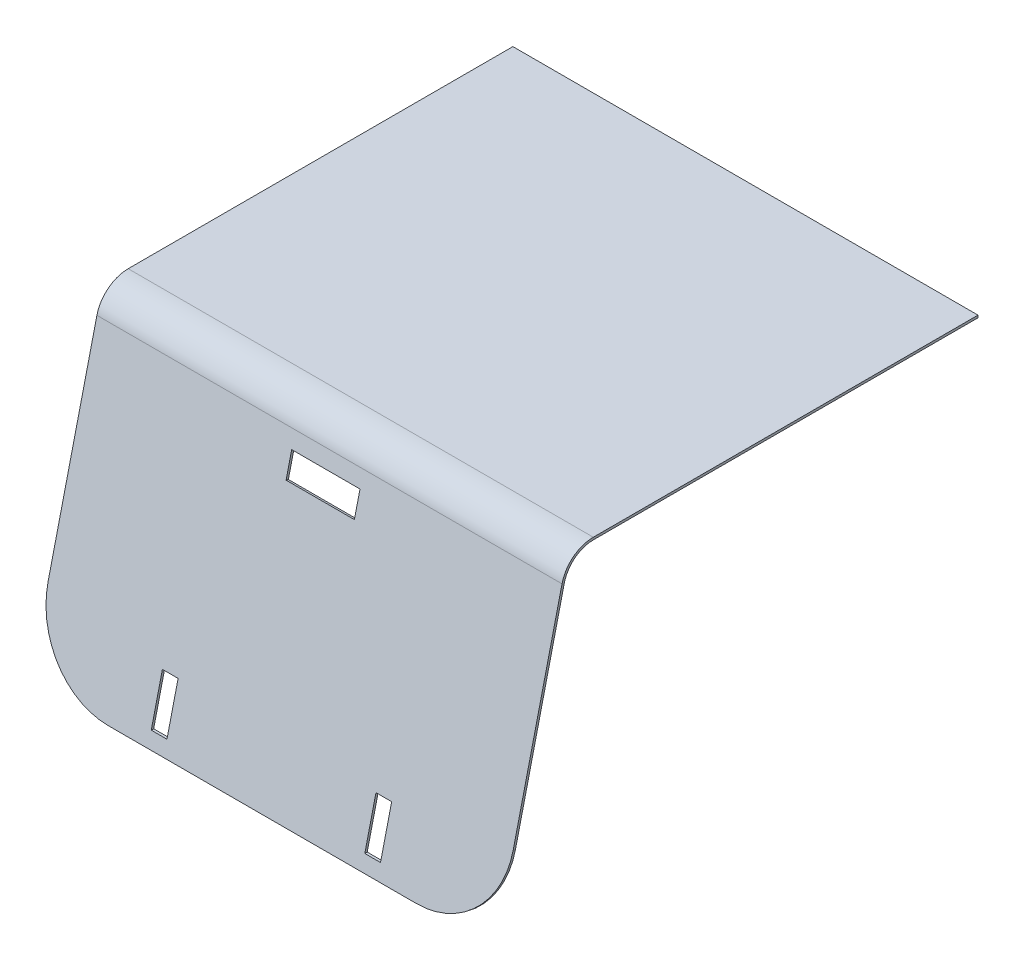
SolidWorks part; units mm, degrees
material "6061 합금"
ref_plane "정면" through (0, 0, 0) normal (0, 0, 1) x (1, 0, 0)
ref_plane "윗면" through (0, 0, 0) normal (0, 1, 0) x (1, 0, 0)
ref_plane "우측면" through (0, 0, 0) normal (1, 0, 0) x (0, 0, -1)
sketch "스케치2" plane through (0, 0, 0) normal (1, 0, 0) x (0, 0, -1)
  line L0 (-245.0866, 321.4745) -> (-245.0866, -319.7255) construction
  line L1 (-215.0866, 321.4745) -> (-215.0866, -319.7255) construction
  line L2 (244.9134, 321.4745) -> (244.9134, -159.7255) construction
  line L3 (214.9134, 321.4745) -> (214.9134, -159.7255) construction
  line L4 (-245.0866, -129.7255) -> (244.9134, -129.7255) construction
  line L5 (-245.0866, -159.7255) -> (244.9134, -159.7255) construction
  line L6 (-245.0866, 20.2745) -> (244.9134, 20.2745) construction
  line L7 (-245.0866, -9.7255) -> (244.9134, -9.7255) construction
  line L8 (-245.0866, 101.2745) -> (244.9134, 101.2745) construction
  line L9 (-245.0866, 71.2745) -> (244.9134, 71.2745) construction
  line L10 (44.9134, -319.7255) -> (44.9134, -129.7255) construction
  line L11 (14.9134, -129.7255) -> (14.9134, -319.7255) construction
  line L12 (154.9134, -129.7255) -> (154.9134, -159.7255) construction
  line L13 (124.9134, -129.7255) -> (124.9134, -159.7255) construction
  line L14 (-180.0866, -285.7255) -> (-180.0866, -319.7255) construction
  line L15 (-180.0866, -319.7255) -> (-120.0866, -319.7255) construction
  line L16 (-120.0866, -319.7255) -> (-120.0866, -285.7255) construction
  line L17 (-248.0866, -129.7255) -> (-317.0866, -129.7255) construction
  line L18 (-317.0866, -129.7255) -> (-317.0866, -124.7255) construction
  line L19 (-317.0866, -124.7255) -> (-245.0866, -124.7255) construction
  line L20 (-248.0866, -79.7255) -> (-248.0866, -129.7255) construction
  line L21 (-317.0866, -124.7255) -> (-317.0866, -79.7255) construction
  line L22 (-317.0866, -79.7255) -> (-248.0866, -79.7255) construction
  line L23 (-366.6673, -141.9832) -> (-319.0575, -312.6598) construction
  line L24 (-309.7511, -319.7255) -> (44.9134, -319.7255) construction
  line L25 (-245.0866, 321.4745) -> (244.9134, 321.4745) construction
  line L26 (-357.3609, -129.7255) -> (-248.0866, -129.7255) construction
  line L27 (-248.0866, -79.7255) -> (-357.8699, -79.7255) construction
  line L28 (-281.0866, -124.7255) -> (-281.0866, -79.7255) construction
  line L29 (-367.2716, -67.8376) -> (-281.9991, 292.2817) construction
  line L30 (-245.0866, 20.2745) -> (-346.4076, 20.2745) construction
  line L31 (281.0076, 291.6281) -> (365.9454, -152.5713) construction
  line L32 (360.9237, -163.222) -> (101.231, -305.3247) construction
  line L33 (-347.8609, 9.7969) -> (-359.3573, -38.7543) construction
  line L34 (-367.2716, -67.8376) -> (-370.1909, -67.1464)
  line L36 (-370.1909, -67.1464) -> (-284.9184, 292.973)
  line L37 (-245.0866, 324.4745) -> (244.9134, 324.4745)
  line L43 (244.9134, 324.4745) -> (244.9134, 321.4745)
  line L45 (244.9134, 321.4745) -> (-245.0866, 321.4745)
  line L48 (-281.9991, 292.2817) -> (-367.2716, -67.8376)
  arc A0 (-120.0866, -285.7255) -> (-180.0866, -285.7255) centre (-150.0866, -285.7255) ccw construction
  arc A1 (-309.7511, -319.7255) -> (-319.0575, -312.6598) centre (-309.7511, -310.0638) cw construction
  arc A2 (-366.6673, -141.9832) -> (-357.3609, -129.7255) centre (-357.3609, -139.3872) cw construction
  arc A3 (-357.8699, -79.7255) -> (-367.2716, -67.8376) centre (-357.8699, -70.0638) cw construction
  arc A4 (365.9454, -152.5713) -> (360.9237, -163.222) centre (356.1234, -154.4495) cw construction
  arc A5 (281.0076, 291.6281) -> (244.9134, 321.4745) centre (244.9134, 284.7263) ccw construction
  arc A6 (44.9134, -319.7255) -> (101.231, -305.3247) centre (44.9134, -202.4043) ccw construction
  arc A7 (-245.0866, 321.4745) -> (-281.9991, 292.2817) centre (-245.0866, 283.5412) ccw construction
  arc A8 (-284.9184, 292.973) -> (-245.0866, 324.4745) centre (-245.0866, 283.5412) cw
  arc A10 (-281.9991, 292.2817) -> (-245.0866, 321.4745) centre (-245.0866, 283.5412) cw
  point P28 (154.9134, -144.7255)
  point P46 (-275.0866, 321.4745)
  point P56 (274.9134, 321.4745)
  point P57 (74.9134, -319.7255)
  dimension "D14" = 60
  dimension "D18" = 30
  dimension "D19" = 30
  dimension "D20" = 30
  dimension "D21" = 10
  dimension "D1" = 30
  dimension "D2" = 490
  dimension "D3" = 30
  dimension "D4" = 30
  dimension "D5" = 150
  dimension "D6" = 30
  dimension "D7" = 81
  dimension "D8" = 30
  dimension "D9" = 290
  dimension "D10" = 30
  dimension "D11" = 110
  dimension "D12" = 30
  dimension "D13" = 95
  dimension "D15" = 72
  dimension "D16" = 5
  dimension "D17" = 45
  dimension "D22" = 3
  dimension "D23" = 72
  dimension "D24" = 1
  dimension "D25" = 3
extrude "보스-돌출1" add sketch "스케치2" along normal blind 296.2 and the other way blind 296.2 contours L48 A10 L45 L43 L37 A8 L36 L34 region at (0, -60.3927, 367.0502)
ref_plane "평면1" through (0, 0, 380) normal (0, 0, 1) x (1, 0, 0)
sketch "스케치3" plane through (0, 0, 380) normal (0, 0, 1) x (1, 0, 0)
  line L0 (-206, 20.9636) -> (206, 20.9636)
  line L1 (0, 20.9636) -> (0, -28.2188) construction
  line L2 (-146, 10.9636) -> (-126, 10.9636)
  line L3 (-146, 10.9636) -> (-146, -49.0364)
  line L4 (-146, -49.0364) -> (-126, -49.0364)
  line L5 (-126, 10.9636) -> (-126, -49.0364)
  line L6 (146, -49.0364) -> (126, -49.0364)
  line L7 (126, 10.9636) -> (126, -49.0364)
  line L8 (146, 10.9636) -> (126, 10.9636)
  line L9 (146, 10.9636) -> (146, -49.0364)
  line L11 (-298, -67.1464) -> (298, -67.1464)
  line L13 (-43.5, 278.473) -> (43.5, 278.473)
  line L14 (-43.5, 278.473) -> (-43.5, 247.473)
  line L15 (-43.5, 247.473) -> (43.5, 247.473)
  line L16 (43.5, 278.473) -> (43.5, 247.473)
  line L17 (-43.5, 278.473) -> (43.5, 247.473) construction
  line L18 (-43.5, 247.473) -> (43.5, 278.473) construction
  line L19 (-296.2, 292.973) -> (296.2, 292.973) construction
  line L21 (-296.2, -67.1464) -> (296.2, -67.1464) construction
  point P12 (0, 262.973)
  dimension "D1" = 60
  dimension "D2" = 20
  dimension "D3" = 10
  dimension "D4" = 126
  dimension "D5" = 88.11
  dimension "D6" = 31
  dimension "D7" = 87
  dimension "D8" = 30
extrude "컷-돌출1" cut sketch "스케치3" against normal up to next contours L9 L8 L7 L6 | L5 L2 L3 L4 region at (-136, -19.0364, 380) region at (136, -19.0364, 380)
ref_plane "평면2" through (0, -70, 0) normal (0, 1, 0) x (1, 0, 0)
fillet "필렛1" radius 100 2 edges at (-296.2, -67.492, 368.7313) (296.2, -67.492, 368.7313)
sketch "스케치10" plane through (0, 79.4385, 335.4811) normal (0, 0.2304, 0.9731) x (1, 0, 0)
  line L0 (0, -0.3516) -> (0, 211.5094) construction
  line L1 (-43.5, 199.4392) -> (43.5, 199.4392)
  line L2 (-43.5, 199.4392) -> (-43.5, 168.4392)
  line L3 (-43.5, 168.4392) -> (43.5, 168.4392)
  line L4 (43.5, 199.4392) -> (43.5, 168.4392)
  line L5 (-43.5, 199.4392) -> (43.5, 168.4392) construction
  line L6 (-43.5, 168.4392) -> (43.5, 199.4392) construction
  line L7 (-296.2, 219.4392) -> (296.2, 219.4392) construction
  point P2 (0, 183.9392)
  dimension "D1" = 31
  dimension "D2" = 87
  dimension "D3" = 20
extrude "컷-돌출2" cut sketch "스케치10" against normal up to next
sketch "스케치11" plane through (0, 79.4385, 335.4811) normal (0, 0.2304, 0.9731) x (1, 0, 0)
  line L5 (251.9, -150.6382) -> (251.9, -12.8916) construction
  line L6 (196.2, -50.6382) -> (266.9107, -121.3489) construction
  line L7 (238.9, -86.8382) -> (238.9, -81.8382) construction
  line L8 (241.9, -104.8382) -> (261.9, -104.8382) construction
  line L9 (241.9, -104.8382) -> (241.9, -107.8382) construction
  line L11 (293.8674, -150.6382) -> (296.2, -150.6382) construction
  line L12 (296.2, -150.6382) -> (296.2, 219.4392) construction
  line L13 (241.9, -107.8382) -> (261.9, -107.8382) construction
  line L14 (261.9, -104.8382) -> (261.9, -107.8382) construction
  line L15 (241.9, -104.8382) -> (261.9, -107.8382) construction
  line L16 (241.9, -107.8382) -> (261.9, -104.8382) construction
  line L17 (241.9, -104.8382) -> (261.9, -104.8382) construction
  line L18 (241.9, -104.8382) -> (241.9, -92.8382) construction
  line L19 (241.9, -92.8382) -> (261.9, -92.8382) construction
  line L20 (261.9, -104.8382) -> (261.9, -92.8382) construction
  line L21 (238.9, -113.8382) -> (264.9, -113.8382) construction
  line L22 (238.9, -113.8382) -> (238.9, -86.8382) construction
  line L23 (238.9, -86.8382) -> (264.9, -86.8382) construction
  line L24 (264.9, -113.8382) -> (264.9, -86.8382) construction
  line L25 (238.9, -113.8382) -> (264.9, -86.8382) construction
  line L26 (238.9, -86.8382) -> (264.9, -113.8382) construction
  line L27 (238.9, -81.8382) -> (264.9, -81.8382) construction
  line L28 (264.9, -81.8382) -> (264.9, -86.8382) construction
  line L29 (296.2, 219.4392) -> (293.8674, 219.4392)
  line L30 (-196.2, -150.6382) -> (196.2, -150.6382) construction
  line L31 (296.2, -50.6382) -> (296.2, 219.4392) construction
  line L32 (261.9, -104.8382) -> (241.9, -104.8382)
  line L33 (261.9, -104.8382) -> (261.9, -107.8382)
  line L34 (261.9, -107.8382) -> (241.9, -107.8382)
  line L35 (241.9, -104.8382) -> (241.9, -107.8382)
  line L36 (261.9, -104.8382) -> (241.9, -107.8382) construction
  line L37 (261.9, -107.8382) -> (241.9, -104.8382) construction
  circle A0 centre (196.2, -50.6382) radius 100 construction
  point P2 (251.9, -106.3382)
  point P9 (251.9, -106.3382)
  point P16 (251.9, -100.3382)
  point P28 (251.9, -106.3382)
  dimension "D2" = 200
  dimension "D1" = 44.3
  dimension "D3" = 45
  dimension "D4" = 20
  dimension "D5" = 3
  dimension "D6" = 12
  dimension "D7" = 7.5
  dimension "D8" = 6
  dimension "D9" = 3
  dimension "D10" = 5
extrude "보스-돌출2" add sketch "스케치11" against normal blind 13 contours L32 L35 L34 L33 region at (251.9, -24.0384, 359.9834)
sketch "스케치12" plane through (0, -102.0172, 24.1566) normal (0, 0.9731, -0.2304) x (1, 0, 0)
  line L0 (261.9, -331.758) -> (261.9, -341.758) construction
  line L1 (241.9, -331.758) -> (261.9, -331.758)
  line L2 (241.9, -331.758) -> (241.9, -334.758)
  line L3 (241.9, -334.758) -> (261.9, -334.758)
  line L4 (261.9, -331.758) -> (261.9, -334.758)
  dimension "D1" = 3
extrude "보스-돌출3" add sketch "스케치12" along normal blind 9
mirror "대칭 복사1" about plane through (0, 0, 0) normal (1, 0, 0) of "보스-돌출3", "보스-돌출2"
